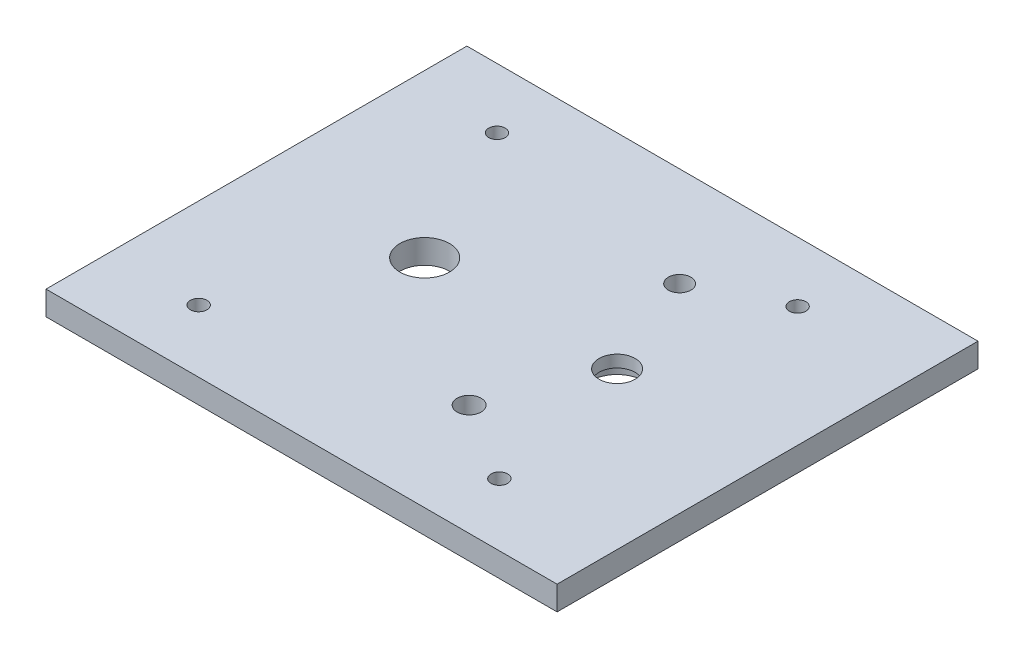
SolidWorks part; units mm, degrees
ref_plane "Front Plane" through (0, 0, 0) normal (0, 0, 1) x (1, 0, 0)
ref_plane "Top Plane" through (0, 0, 0) normal (0, 1, 0) x (1, 0, 0)
ref_plane "Right Plane" through (0, 0, 0) normal (1, 0, 0) x (0, 0, -1)
sketch "Sketch1" plane through (0, 0, 0) normal (0, 1, 0) x (1, 0, 0)
  line L0 (0, 8.2993) -> (0, -7.906) construction
  line L1 (-42.5, 35) -> (42.5, 35)
  line L2 (-42.5, 35) -> (-42.5, -35)
  line L3 (-42.5, -35) -> (42.5, -35)
  line L4 (42.5, 35) -> (42.5, -35)
  line L5 (-42.5, 35) -> (42.5, -35) construction
  line L6 (-42.5, -35) -> (42.5, 35) construction
  line L7 (-12.4915, 0.1967) -> (14.4413, 0.1967) construction
  line L8 (9.5, 1) -> (10.7497, 1) construction
  line L9 (37.5085, 0.1967) -> (64.4413, 0.1967) construction
  line L11 (15.0001, 2.9838) -> (15.0001, -1.0162)
  line L13 (17.9999, 3.0162) -> (17.9999, -0.9838)
  line L14 (15.0001, 2.9838) -> (17.9999, -0.9838) construction
  line L15 (15.0001, -1.0162) -> (17.9999, 3.0162) construction
  circle A0 centre (-27.5, 25) radius 1.375
  circle A1 centre (22.5, 25) radius 1.375
  circle A2 centre (22.5, -24.6067) radius 1.375
  circle A3 centre (-27.5, -24.6067) radius 1.375
  circle A4 centre (16.5, 1) radius 10
  circle A5 centre (-15.52, 1) radius 20
  arc A6 (15.0001, 2.9838) -> (17.9999, 3.0162) centre (16.5217, 1.0001) cw
  arc A7 (15.0001, -1.0162) -> (17.9999, -0.9838) centre (16.4783, 0.9999) ccw
  circle A8 centre (16.4783, 0.9999) radius 4.5
  circle A12 centre (-15.52, 1) radius 4.125
  circle A13 centre (16.4783, 0.9999) radius 3
  circle A14 centre (9.5, 1) radius 14
  circle A17 centre (85.0307, -10.8481) radius 14
  circle A18 centre (86.1334, -28.3481) radius 2
  circle A19 centre (86.1334, 6.6519) radius 2
  circle A20 centre (9.5, 1) radius 14
  circle A21 centre (9.4072, 18.471) radius 1.875
  circle A22 centre (9.4014, -16.529) radius 2
  point P0 (0, 0)
  dimension "D3" = 15
  dimension "D6" = 2.75
  dimension "D7" = 26
  dimension "D10" = 32.02
  dimension "D11" = 9
  dimension "D12" = 7
  dimension "D13" = 3.75
  dimension "D15" = 1.1027
  dimension "D17" = 1.1027
  dimension "D20" = 8.25
  dimension "D21" = 6
  dimension "D1" = 85
  dimension "D2" = 70
  dimension "D4" = 10
  dimension "D8" = 4
  dimension "D9" = 3
  dimension "D18" = 36
  dimension "D19" = 4
  dimension "D22" = 28.9915
  dimension "D5" = 2
extrude "Boss-Extrude4" add sketch "Sketch1" along normal blind 4 contours L4 L1 L2 L3 A14 A4 A5 A2 A1 A0 A3 | A14 A5 | A14 A4 | A5 A14 A4 | A5 A14 | A4 A14 A8 | A8 A13 | A4 A14 A5 region at (0, 0, -33.8989) region at (23.9705, 0, -1) region at (22.3127, 0, -5.9551) region at (6.1628, 0, -1) region at (-5.0421, 0, -1) region at (0.1582, 0, -1) region at (12.1056, 0, -0.9999)
sketch "Sketch2" plane through (0, 4, 0) normal (0, 1, 0) x (1, 0, 0)
  circle A3 centre (-15.52, 1) radius 9.125
  circle A4 centre (-15.52, 1) radius 9.125
  dimension "D1" = 5
extrude "Cut-Extrude2" cut sketch "Sketch1<7>" along normal blind 2 contours A8
sketch "Sketch1<7>" plane through (0, 0, 0) normal (0, 1, 0) x (1, 0, 0) same geometry as "Sketch1"
